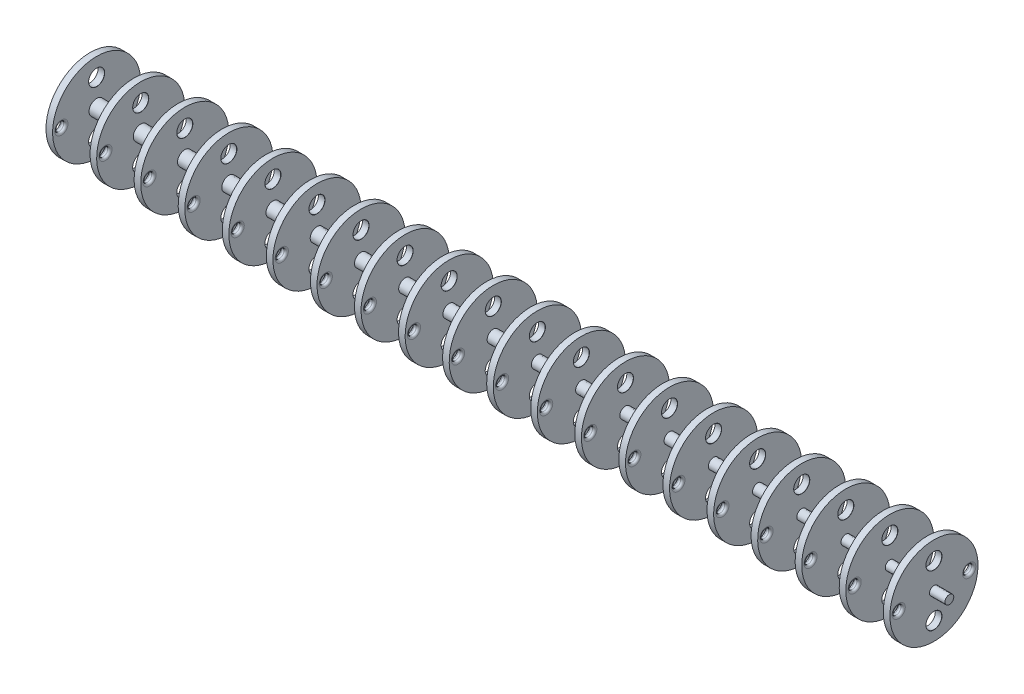
SolidWorks part; units mm, degrees
ref_plane "Front Plane" through (0, 0, 0) normal (0, 0, 1) x (1, 0, 0)
ref_plane "Top Plane" through (0, 0, 0) normal (0, 1, 0) x (1, 0, 0)
ref_plane "Right Plane" through (0, 0, 0) normal (1, 0, 0) x (0, 0, -1)
sketch "Sketch2" plane through (0, 0, 0) normal (0, 0, 1) x (1, 0, 0)
  line L0 (0, 1.75) -> (200, 1)
  line L1 (0, -11) -> (0, 11) construction
  line L2 (200, 1) -> (200, 0)
  line L3 (200, 0) -> (0, 0)
  line L4 (0, 0) -> (0, 1.75)
  dimension "D1" = 1.75
  dimension "D2" = 200
  dimension "D3" = 1
revolve "Revolve1" add sketch "Sketch2" angle 360 about L3
ref_axis "Axis1" through (-3.9062, 0, 0) along (1, 0, 0)
sketch "Sketch3" plane through (0, 0, 0) normal (0, 0, 1) x (1, 0, 0)
  line L0 (5, 0) -> (5, 10)
  line L1 (5, 10) -> (6.5, 10)
  line L2 (6.5, 10) -> (6.5, 0)
  line L3 (6.5, 0) -> (5, 0)
  line L4 (0, -11) -> (0, 11) construction
  dimension "D1" = 1.5
  dimension "D2" = 10
  dimension "D3" = 5
revolve "Revolve2" add sketch "Sketch3" angle 360 about L3
sketch "Sketch5" plane through (6.5, 0, 0) normal (1, 0, 0) x (0, 0, -1)
  line L0 (-8, 0) -> (0, 0) construction
  line L1 (0, 0) -> (8, 0) construction
  circle A0 centre (-8, 0) radius 1
  circle A1 centre (8, 0) radius 1
  dimension "D2" = 2
  dimension "D1" = 8
extrude "Cut-Extrude1" cut sketch "Sketch5" against normal up to next
fillet "Fillet1" radius 0.5 4 edges at (5, -1, -8) (5, -1, 8) (6.5, 1, 8) (6.5, 1, -8)
hole_wizard "M3 Clearance Hole1" positions "Sketch14" profile "Sketch15" hole size "M3" standard "ANSI Metric" end condition up to next
sketch "Sketch14" plane through (6.5, 0, 0) normal (1, 0, 0) x (0, 0, -1)
  line L0 (0, 1.7256) -> (0, 10) construction
  line L1 (0, 11) -> (0, -11) construction
  line L3 (0, -1.7256) -> (0, -10.0561) construction
  circle A0 centre (0, 0) radius 1.7256 construction
  circle A1 centre (0, 0) radius 10 construction
  point P15 (0, 5.8628)
  point P17 (0, -5.8909)
sketch "Sketch15" plane through (6.5, -5.8909, 0) normal (0, 1, 0) x (0, 0, -1)
  line L0 (0, 0) -> (0, 1.5)
  line L1 (0, 1.5) -> (1.8, 1.5)
  line L2 (1.8, 1.5) -> (1.8, 0.025)
  line L3 (1.8, 0.025) -> (1.825, 0)
  line L5 (1.825, 0) -> (0, 0)
  line L6 (-1.8, 0.025) -> (-1.825, 0) construction
  line L11 (0, -6.35) -> (0, 107.95) construction
  dimension "Thru Hole Dia." = 3.6
  dimension "Thru Hole Depth" = 1.5
  dimension "Near C'Sink Dia." = 3.65
  dimension "Near C'Sink Angle" = 90
pattern_linear "LPattern1" count 20 spacing 10 along (1, 0, 0) of "Revolve2", "Cut-Extrude1", "Fillet1", "M3 Clearance Hole1"
equation "\"R_initial\"= 1.75"
equation "\"D1@Sketch2\"=\"R_initial\""
equation "\"R_distal\"= 1"
equation "\"D3@Sketch2\"=\"R_distal\""
equation "\"L\"=200"
equation "\"D2@Sketch2\"=\"L\""
equation "\"disk_thickness\"= 1.5"
equation "\"D1@Sketch3\"=\"disk_thickness\""
equation "\"disk_radius\"=10"
equation "\"D2@Sketch3\"=\"disk_radius\""
equation "\"disk_spacing_initial\"=5"
equation "\"D3@Sketch3\"=\"disk_spacing_initial\""
equation "\"tendon_routing_radius\"=8"
equation "\"D1@Sketch5\"=\"tendon_routing_radius\""
equation "\"tendon_routing_hole_radius\"=2"
equation "\"D2@Sketch5\"=\"tendon_routing_hole_radius\""
equation "\"tendon_routing_hole_fillet\"=0.5"
equation "\"D1@Fillet1\"=\"tendon_routing_hole_fillet\""
equation "\"inter_disk_spacing\"=10"
equation "\"D3@LPattern1\"=\"inter_disk_spacing\""
equation "\"num_disk\"= 20"
equation "\"D1@LPattern1\"=\"num_disk\""
